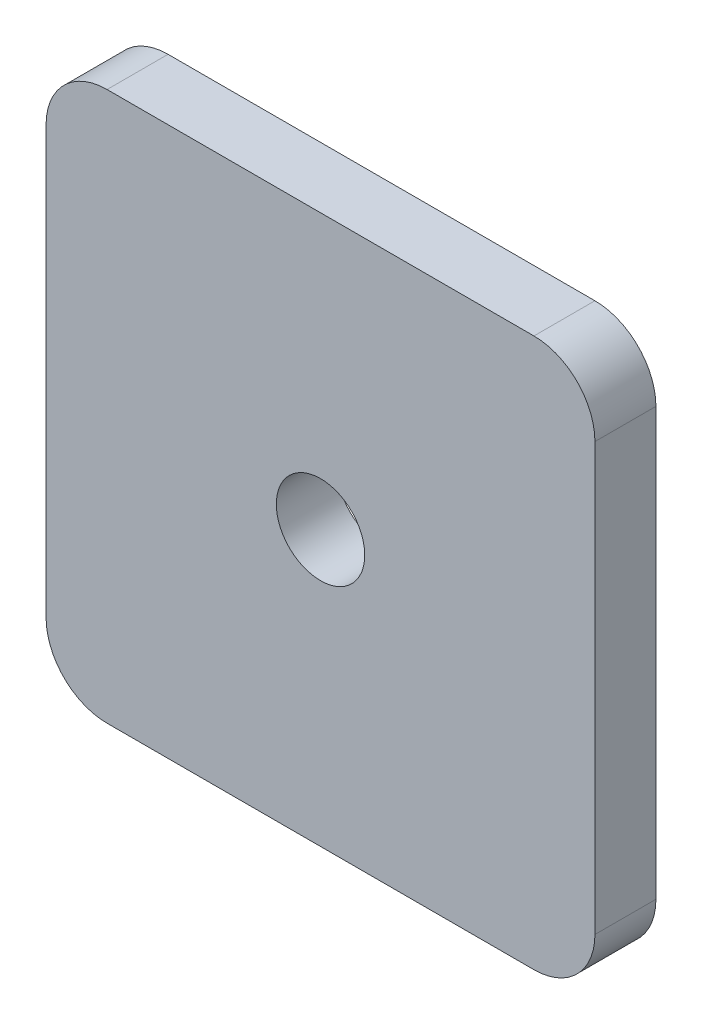
SolidWorks part; units mm, degrees
material "1.4003 (X2CrNi12)"
ref_plane "Ön Düzlem" through (0, 0, 0) normal (0, 0, 1) x (1, 0, 0)
ref_plane "Üst Düzlem" through (0, 0, 0) normal (0, 1, 0) x (1, 0, 0)
ref_plane "Sağ Düzlem" through (0, 0, 0) normal (1, 0, 0) x (0, 0, -1)
sketch "Çizim1" plane through (0, 0, 0) normal (0, 0, 1) x (1, 0, 0)
  line L1 (-45, 45) -> (45, 45)
  line L2 (-45, 45) -> (-45, -45)
  line L3 (-45, -45) -> (45, -45)
  line L4 (45, 45) -> (45, -45)
  line L5 (-45, 45) -> (45, -45) construction
  line L6 (-45, -45) -> (45, 45) construction
  circle A0 centre (0, 0) radius 7.25
  point P0 (0, 0)
  dimension "D3" = 14.5
  dimension "D1" = 90
  dimension "D2" = 90
base flange "Taban-Flanş1" sketch "Çizim1" thickness 10 reverse thickness direction no parameters "D1"=5
cosmetic thread "Kozmetik Diş Açma1" parameters "D2"=16
fillet "Radyus1" radius 10 4 edges at (-45, 45, -5) (45, 45, -5) (45, -45, -5) (-45, -45, -5)
sketch "Büküm-Çizgileri1" [suppressed] plane through (0, 0, 0) normal (0, 1, 0) x (1, 0, 0)
sketch "Sınırlandırma-Kutusu1" [suppressed] plane through (0, 0, 0) normal (0, 1, 0) x (1, 0, 0)
sheet metal parameters "Sac-Levha1" thickness 10 parameters "D1"=5
flat pattern "Düz-Çoğaltma1" [suppressed]
sketch "Büküm-Çizgileri2" plane through (0, 0, 0) normal (0, 1, 0) x (1, 0, 0)
sketch3d "Sınırlandırma-Kutusu2" [suppressed]
  line L0 (-45, -45, 0) -> (45, -45, 0) construction
  line L1 (-45, 45, 0) -> (45, 45, 0) construction
  line L2 (-45, -45, 0) -> (-45, 45, 0) construction
  line L3 (45, -45, 0) -> (45, 45, 0) construction
